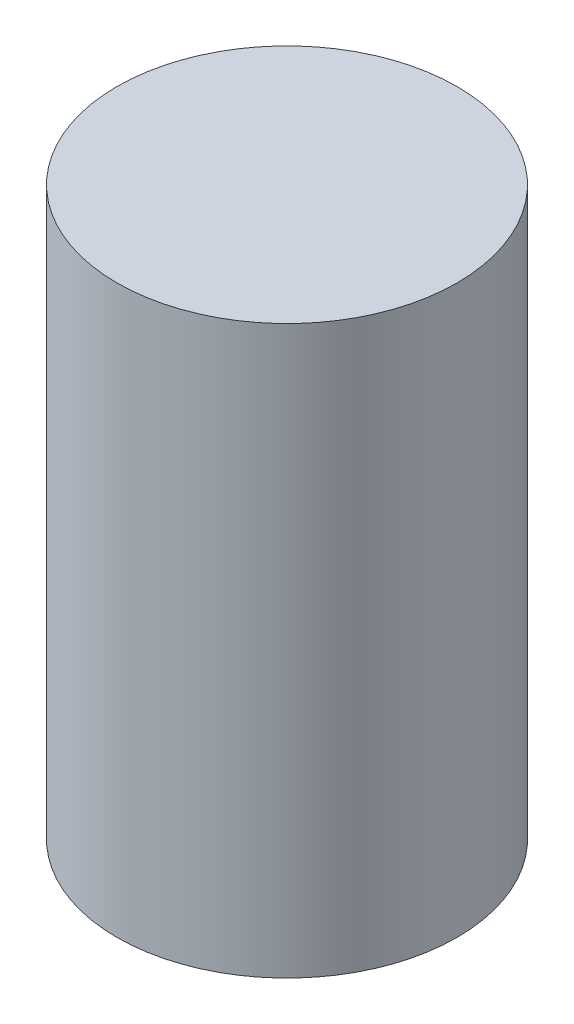
SolidWorks part; units mm, degrees
ref_plane "Front Plane" through (0, 0, 0) normal (0, 0, 1) x (1, 0, 0)
ref_plane "Top Plane" through (0, 0, 0) normal (0, 1, 0) x (1, 0, 0)
ref_plane "Right Plane" through (0, 0, 0) normal (1, 0, 0) x (0, 0, -1)
sketch "Sketch1" plane through (0, 0, 0) normal (0, 1, 0) x (1, 0, 0)
  circle A0 centre (0, 0) radius 1.5
  dimension "D1" = 3
extrude "Boss-Extrude1" add sketch "Sketch1" along normal blind 5 contours A0
